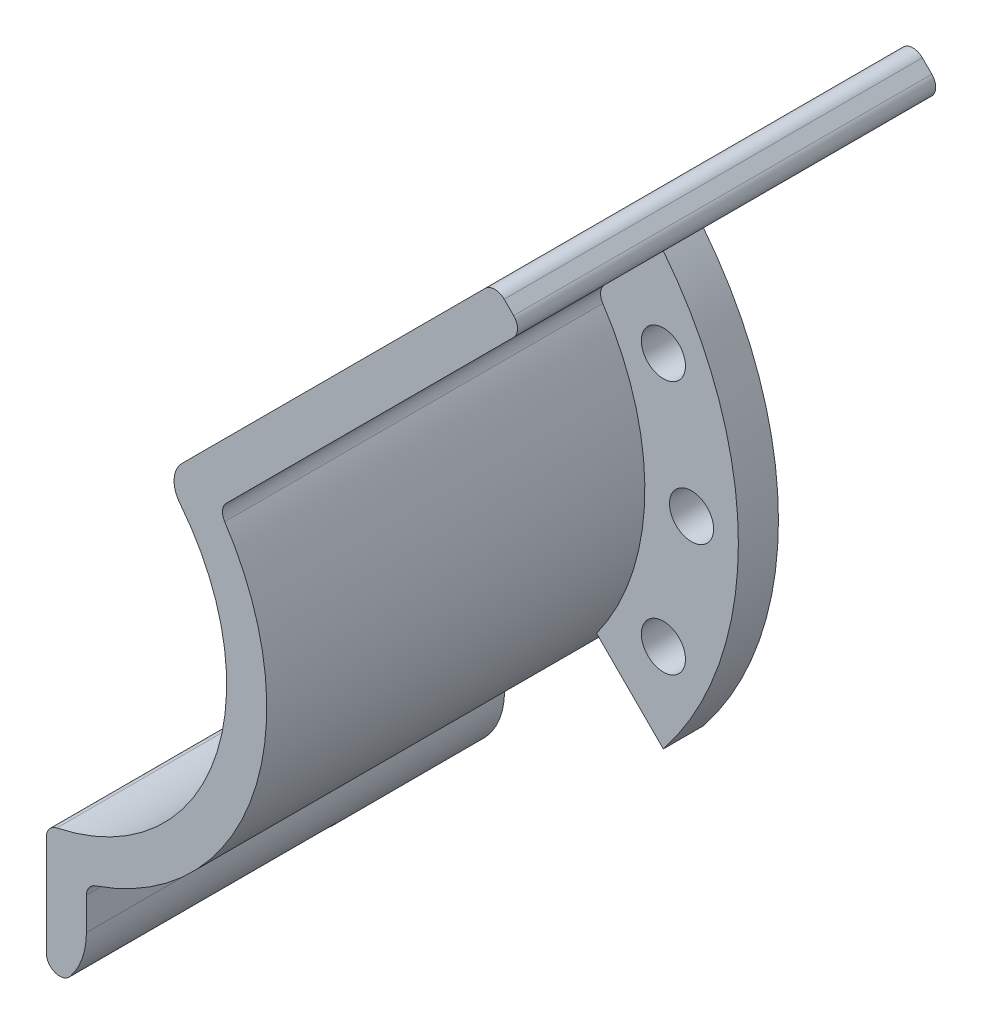
SolidWorks part; units mm, degrees
ref_plane "前视基准面" through (0, 0, 0) normal (0, 0, 1) x (1, 0, 0)
ref_plane "上视基准面" through (0, 0, 0) normal (0, 1, 0) x (1, 0, 0)
ref_plane "右视基准面" through (0, 0, 0) normal (1, 0, 0) x (0, 0, -1)
sketch "草图1" plane through (0, 0, -1.3) normal (0, 0, 1) x (1, 0, 0)
  line L0 (36.0624, 36.0624) -> (11.3137, 11.3137)
  line L1 (0, 23.564) -> (0, -22.8784) construction
  line L3 (2.5, -15.8035) -> (2.5, -18.8348)
  line L4 (1.5, -13.5) -> (1.5, -14.3614) construction
  line L5 (36.0624, 36.0624) -> (38.1838, 33.9411)
  line L6 (38.1838, 33.9411) -> (15.3878, 11.1452)
  arc A0 (11.9682, -9.0422) -> (14.8566, -2.069) centre (0, 0) ccw construction
  arc A2 (2.5, -18.8348) -> (15.3878, 11.1452) centre (0, 0) ccw
  arc A3 (2.5, -15.8035) -> (11.3137, 11.3137) centre (0, 0) ccw
  point P20 (1.5, -13.9307)
  dimension "D1" = 1
  dimension "D4" = 45
  dimension "D2" = 3
  dimension "D3" = 35
  dimension "D5" = 1
  dimension "D6" = 3
extrude "凸台-拉伸1" add sketch "草图1" along normal up to surface (31.3 mm away)
sketch "草图2" plane through (0, 0, -1.3) normal (0, 0, 1) x (1, 0, 0)
  line L0 (15.3878, 11.1452) -> (38.1838, 33.9411) construction
  line L1 (0, 0) -> (31.8729, 0) construction
  line L2 (15.3878, 11.1452) -> (38.1838, 33.9411) construction
  line L3 (15.3878, 11.1452) -> (20.3833, 16.1407)
  line L4 (15.3878, -11.1452) -> (20.3833, -16.1407)
  arc A0 (20.3833, 16.1407) -> (20.3833, -16.1407) centre (0, 0) cw
  arc A2 (2.5, -18.8348) -> (15.3878, 11.1452) centre (0, 0) ccw construction
  arc A3 (15.3878, -11.1452) -> (15.3878, 11.1452) centre (0, 0) ccw
  arc A4 (17.8856, -13.6429) -> (17.8856, 13.6429) centre (0, 0) ccw construction
  dimension "D1" = 26
extrude "凸台-拉伸2" add sketch "草图2" along normal blind 3
sketch "草图8" plane through (0, 0, -1.3) normal (0, 0, 1) x (1, 0, 0)
  line L0 (2.5, -18.8348) -> (2.5, -21.3348)
  line L1 (0, -23.8348) -> (0, -26.8348)
  line L2 (5.5, -21.3348) -> (5.5, -18.1865)
  line L3 (2.5, -21.3348) -> (-1.9026, -21.3348) construction
  line L4 (0, -23.8348) -> (0, -21.3348) construction
  arc A0 (2.5, -21.3348) -> (0, -23.8348) centre (0, -21.3348) cw
  arc A1 (0, -26.8348) -> (5.5, -21.3348) centre (0, -21.3348) ccw
  arc A2 (2.5, -18.8348) -> (15.3878, 11.1452) centre (0, 0) ccw construction
  arc A4 (2.5, -18.8348) -> (15.3878, -11.1452) centre (0, 0) ccw construction
  arc A5 (2.5, -18.8348) -> (5.5, -18.1865) centre (0, 0) ccw
  point P8 (0, 0)
  dimension "D1" = 3
  dimension "D4" = 2.5
  dimension "D2" = 3
  dimension "D3" = 2.5
extrude "凸台-拉伸3" add sketch "草图8" along normal up to surface (31.3 mm away) up to face at (20.4615, 8.5774, 30)
sketch "草图9" plane through (0, 0, 30) normal (0, 0, 1) x (1, 0, 0)
  line L0 (2.5, -15.8035) -> (2.5, -21.3348) construction
  line L1 (-5.2306, -21.3348) -> (2.5, -21.3348)
  line L2 (-5.2306, -21.3348) -> (-5.2306, -27.3309)
  line L3 (-5.2306, -27.3309) -> (2.5, -27.3309)
  line L4 (2.5, -21.3348) -> (2.5, -27.3309)
extrude "切除-拉伸1" cut sketch "草图9" against normal blind 20
hole_wizard "ST2.9 间隙孔1" positions "草图6" profile "草图7" hole size "ST2.9" standard "GB" end condition through all
sketch "草图6" plane through (0, 0, 1.7) normal (0, 0, 1) x (1, 0, 0)
  line L0 (15.3878, -11.1452) -> (20.3833, -16.1407) construction
  line L1 (15.3878, 11.1452) -> (38.1838, 33.9411) construction
  line L2 (0, 0) -> (22.4949, 0) construction
  line L4 (0, 0) -> (20.3873, 9.5068) construction
  line L6 (0, 0) -> (20.3873, -9.5068) construction
  arc A0 (17.8856, -13.6429) -> (17.8856, 13.6429) centre (0, 0) ccw construction
  point P0 (22.4949, 0)
  point P14 (20.3873, 9.5068)
  point P16 (20.3873, -9.5068)
  dimension "D1" = 25
  dimension "D2" = 25
sketch "草图7" plane through (22.4949, 0, 1.7) normal (1, 0, 0) x (0, -1, 0)
  line L0 (0, 0) -> (0, 3)
  line L1 (0, 3) -> (1.65, 3)
  line L2 (1.65, 3) -> (1.65, 0)
  line L5 (1.65, 0) -> (0, 0)
  line L11 (0, -6.35) -> (0, 107.95) construction
  dimension "通孔孔直径" = 3.3
  dimension "通孔孔深度" = 3
fillet "圆角1" radius 1 6 edges at (2.5, -15.8035, 14.35) (15.3878, 11.1452, 15.85) (38.1838, 33.9411, 14.35) (36.0624, 36.0624, 14.35) (5.5, -18.1865, 14.35) (2.5, -26.2338, 20)
fillet "圆角2" radius 2 1 edges at (11.3137, 11.3137, 14.35)
